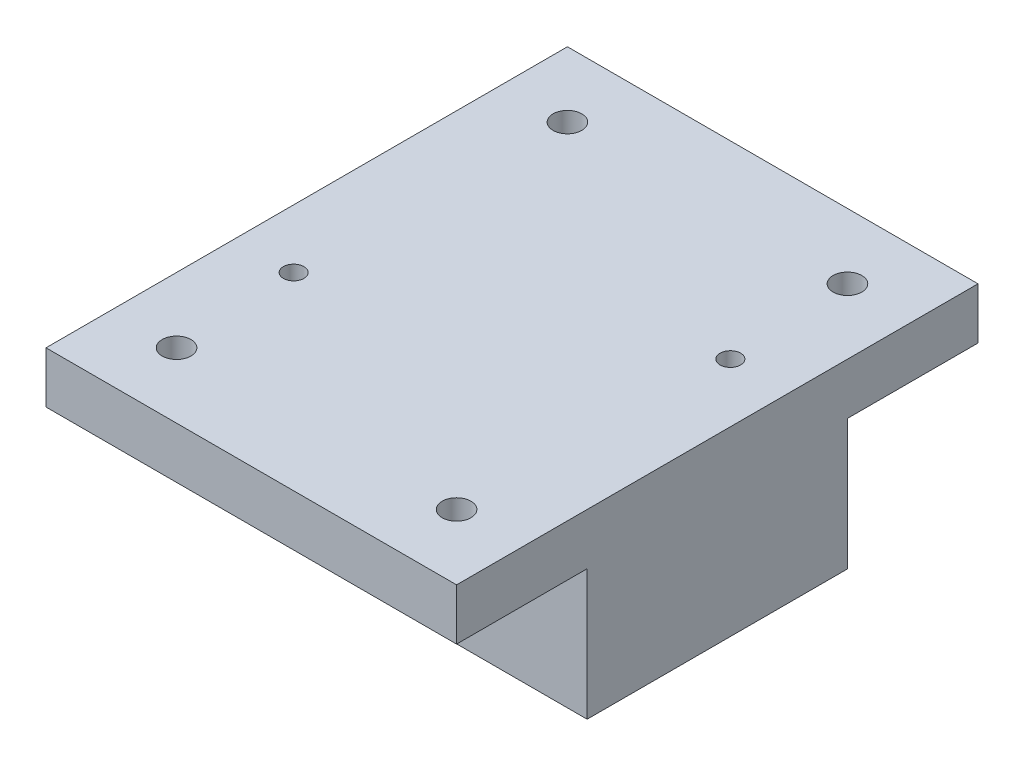
SolidWorks part; units mm, degrees
material "PETG"
ref_plane "Front Plane" through (0, 0, 0) normal (0, 0, 1) x (1, 0, 0)
ref_plane "Top Plane" through (0, 0, 0) normal (0, 1, 0) x (1, 0, 0)
ref_plane "Right Plane" through (0, 0, 0) normal (1, 0, 0) x (0, 0, -1)
sketch "Sketch1" plane through (0, 0, 0) normal (0, 1, 0) x (1, 0, 0)
  line L0 (-27.2813, 38.0813) -> (-27.2813, 50.8) construction
  line L1 (-40, -25.3625) -> (40, -25.3625)
  line L2 (-40, -25.3625) -> (-40, 25.3625)
  line L3 (-40, 25.3625) -> (40, 25.3625)
  line L4 (40, -25.3625) -> (40, 25.3625)
  line L5 (-40, 50.8) -> (40, 50.8)
  line L6 (-40, 50.8) -> (-40, -50.8)
  line L7 (-40, -50.8) -> (40, -50.8)
  line L8 (40, 50.8) -> (40, -50.8)
  line L9 (-27.2813, 38.0813) -> (-40, 38.0813) construction
  line L10 (-27.2813, 38.0813) -> (-27.2813, 25.3625) construction
  line L11 (27.2813, 38.0813) -> (40, 38.0813) construction
  line L13 (-27.2813, -38.0812) -> (-27.2813, -25.3625) construction
  circle A0 centre (-27.2813, 38.0813) radius 2.8
  circle A1 centre (27.2813, 38.0813) radius 2.8
  circle A2 centre (-27.2813, -38.0812) radius 2.8
  circle A3 centre (27.2813, -38.0812) radius 2.8
  point P4 (-40, 0)
  point P5 (0, 25.3625)
  dimension "D4" = 5.6
  dimension "D1" = 50.725
  dimension "D2" = 80
  dimension "D3" = 101.6
extrude "Boss-Extrude1" add sketch "Sketch1" along normal blind 10 contours L1 L4 L3 L2 | L8 L1 L6 L7 | L8 L5 L6 L3 region at (0, 0, 0) region at (0, 0, 38.0812) region at (0, 0, -38.0812)
extrude "Boss-Extrude2" add sketch "Sketch1<3>" against normal blind 25.4 contours L1 L4 L3 L2 region at (0, 0, 0)
sketch "Sketch1<3>" plane through (0, 0, 0) normal (0, 1, 0) x (1, 0, 0) same geometry as "Sketch1"
sketch "Sketch2" plane through (0, 10, 0) normal (0, 1, 0) x (1, 0, 0)
  line L0 (-40, 0) -> (40, 0) construction
  line L1 (-40, -50.8) -> (-40, 50.8) construction
  line L2 (40, -50.8) -> (40, 50.8) construction
  line L3 (0, 50.8) -> (0, -50.8) construction
  line L4 (-40, 50.8) -> (40, 50.8) construction
  line L5 (-40, -50.8) -> (40, -50.8) construction
  line L6 (-28.575, -13.97) -> (-28.575, 0) construction
  line L7 (-28.575, -13.97) -> (0, -13.97) construction
  line L8 (28.575, 0) -> (28.575, 13.97) construction
  line L9 (28.575, 13.97) -> (0, 13.97) construction
  circle A0 centre (-28.575, -13.97) radius 2
  circle A1 centre (28.575, 13.97) radius 2
  dimension "D2" = 4
  dimension "D1" = 13.97
  dimension "D3" = 28.575
extrude "Cut-Extrude1" cut sketch "Sketch2" against normal through all
equation "\"tol_dia_id_intfc\" = 0.0500mm ' For hole diameters - Interference fit"
equation "\"tol_dia_id_slip\"  = 0.0750mm ' For hole diameters - Slip fit"
equation "\"tol_dia_id_clear\" = 0.1000mm ' For hole diameters - Clearance fit"
equation "\"tol_dia_od_intfc\" = 0.0500mm ' For shaft diameters - Interference fit"
equation "\"tol_dia_od_slip\"  = 0.0750mm ' For shaft diameters - Slip fit"
equation "\"tol_dia_od_clear\" = 0.1000mm ' For shaft diameters - Clearance fit"
equation "\"tol_general_intfc\"= 0.0250mm ' For general parts (Horiz) - Interference fit"
equation "\"tol_general_slip\" = 0.0375mm ' For general parts (Horiz) - Slip fit"
equation "\"tol_general_clear\"= 0.0500mm ' For general parts (Horiz) - Clearance fit"
equation "\"tol_layer_intfc\"  = 0.0250mm ' For all parts (Vert) - Interference fit"
equation "\"tol_layer_slip\"   = 0.0375mm ' For all parts (Vert) - Slip fit"
equation "\"tol_layer_clear\"  = 0.0500mm ' For all parts (Vert) - Clearance fit"
equation "\"tol_corner_rad\"   = 0.100mm ' For corners that fit into other parts"
equation "\"D1@Sketch1\"=50.80mm-\"tol_general_slip\"*2"
equation "\"D2@Sketch2\"=3.95+\"tol_dia_id_intfc\""
